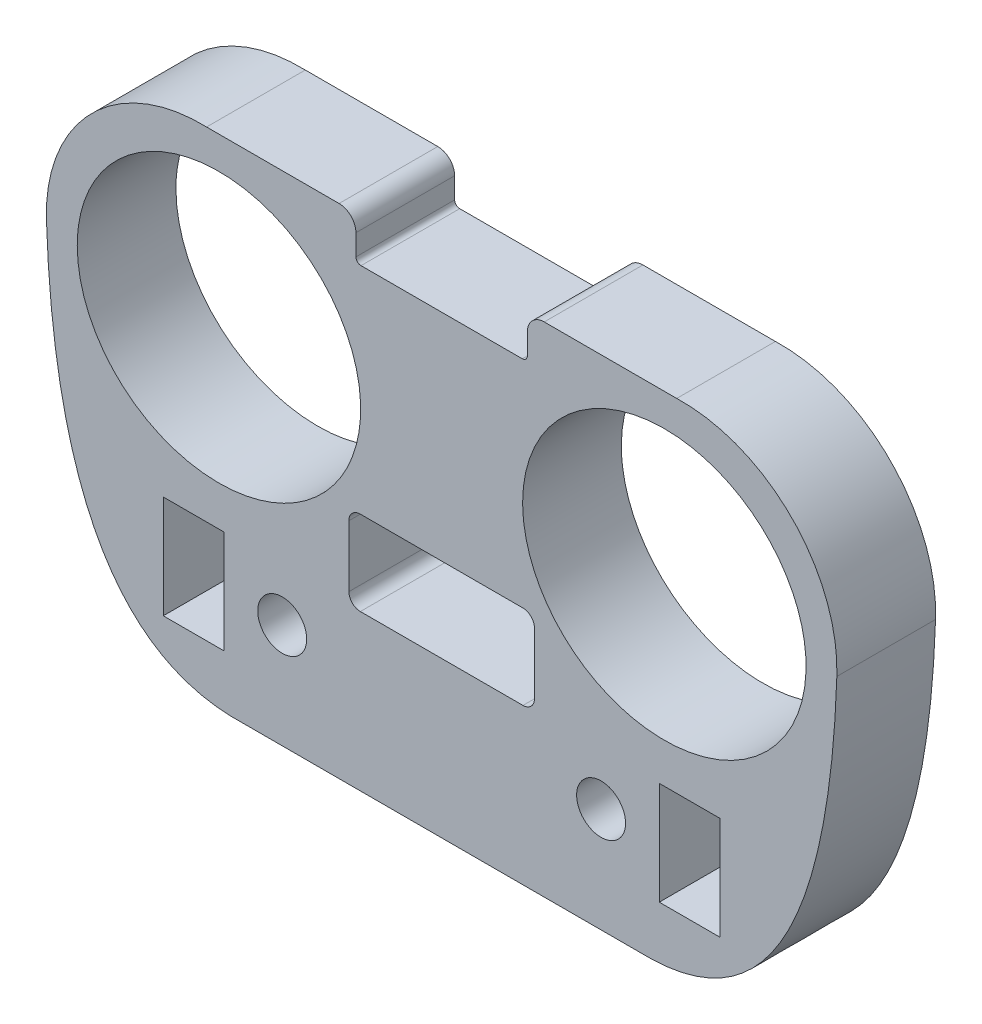
SolidWorks part; units mm, degrees
material "Acrylic (Medium-high impact)"
ref_plane "Front Plane" through (0, 0, 0) normal (0, 0, 1) x (1, 0, 0)
ref_plane "Top Plane" through (0, 0, 0) normal (0, 1, 0) x (1, 0, 0)
ref_plane "Right Plane" through (0, 0, 0) normal (1, 0, 0) x (0, 0, -1)
sketch "Model" plane through (0, 0, 0) normal (0, 0, 1) x (1, 0, 0)
  line L0 (549.8561, 574.3347) -> (554.6761, 574.3347)
  line L1 (554.6761, 576.8347) -> (549.1761, 576.8347) construction
  line L2 (554.6761, 576.8347) -> (560.1761, 576.8347) construction
  line L3 (554.6761, -405.4445) -> (554.6761, 49594.5555) construction
  line L4 (540.7427, 594.6497) -> (549.5961, 594.6497)
  line L5 (542.1922, 565.1247) -> (567.16, 565.1247)
  line L6 (549.8561, 579.3347) -> (554.6761, 579.3347)
  line L7 (567.5761, 574.3747) -> (567.5761, 568.2747)
  line L8 (571.1761, 574.3747) -> (567.5761, 574.3747)
  line L9 (571.1761, 568.2747) -> (571.1761, 574.3747)
  line L10 (567.5761, 568.2747) -> (571.1761, 568.2747)
  line L11 (560.1761, 578.6547) -> (560.1761, 575.0147)
  line L12 (559.4961, 579.3347) -> (554.6761, 579.3347)
  line L13 (559.4961, 574.3347) -> (554.6761, 574.3347)
  line L14 (538.7761, 571.3247) -> (570.5761, 571.3247) construction
  line L15 (541.4761, 584.7347) -> (567.8761, 584.7347) construction
  line L16 (549.5961, 592.1097) -> (559.7561, 592.1097)
  line L17 (549.5961, 592.1097) -> (549.5961, 594.6497)
  line L18 (559.7561, 592.1097) -> (559.7561, 594.6497)
  line L19 (559.7561, 594.6497) -> (568.6095, 594.6497)
  line L20 (541.4761, 584.7347) -> (541.4761, 592.7347) construction
  line L21 (549.1761, 578.6547) -> (549.1761, 575.0147)
  line L32 (541.7761, 568.2747) -> (538.1761, 568.2747)
  line L33 (538.1761, 568.2747) -> (538.1761, 574.3747)
  line L34 (538.1761, 574.3747) -> (541.7761, 574.3747)
  line L35 (541.7761, 574.3747) -> (541.7761, 568.2747)
  circle A0 centre (545.2261, 571.3247) radius 1.45
  arc A1 (578.1008, 585.1247) -> (568.6095, 594.6497) centre (568.8929, 585.4407) ccw
  arc A3 (549.1761, 575.0147) -> (549.8561, 574.3347) centre (549.8561, 575.0147) ccw
  arc A4 (549.1761, 578.6547) -> (549.8561, 579.3347) centre (549.8561, 578.6547) cw
  arc A5 (560.1761, 578.6547) -> (559.4961, 579.3347) centre (559.4961, 578.6547) ccw
  arc A6 (560.1761, 575.0147) -> (559.4961, 574.3347) centre (559.4961, 575.0147) cw
  arc A7 (531.2514, 585.1247) -> (540.7427, 594.6497) centre (540.4593, 585.4407) cw
  circle A9 centre (564.1261, 571.3247) radius 1.45
  ellipse E0 centre (541.4761, 584.7347) end of major axis (533.0761, 584.7347) minor radius 8
  ellipse E1 centre (567.8761, 584.7347) end of major axis (559.4761, 584.7347) minor radius 8
  spline S0 degree 2 poles (578.1008, 585.1247) (577.4253, 565.4445) (567.16, 565.1247) knots 0 0 0 1 1 1
  spline S48 degree 2 poles (531.2514, 585.1247) (531.9269, 565.4445) (542.1922, 565.1247) knots 0 0 0 1 1 1
  point P0 (554.6761, 571.3247)
  point P2 (541.4761, 592.7347)
  point P19 (549.8761, 584.7347)
  point P32 (559.4761, 584.7347)
  point P33 (554.6761, 584.7347)
  point P34 (554.6761, 565.1247)
  point P36 (554.6761, 576.8347)
  point P40 (554.6761, 592.1097)
  dimension "D11" = 2.9
  dimension "D12" = 8
  dimension "D14" = 0.68
  dimension "D16" = 10.16
  dimension "D1" = 3.45
  dimension "D2" = 9.45
  dimension "D3" = 20
  dimension "D4" = 6.1
  dimension "D5" = 11
  dimension "D6" = 5
  dimension "D7" = 3.6
  dimension "D8" = 29.525
  dimension "D9" = 6.2
  dimension "D10" = 0.04
  dimension "D13" = 13.2
  dimension "D15" = 7.9
  dimension "D17" = 2.54
  dimension "D18" = 5.51
  dimension "D19" = 8.4
extrude "Boss-Extrude1" add sketch "Model" along normal blind 5.85 contours A7 S48 L5 S0 A1 L4 A9 L11 A6 L13 L0 A3 L21 A4 L6 L12 A5 E0 A0 L10 L7 L8 L9 L34 L35 L32 L33 E1 region at (545.1694, 594.0958, 0)
fillet "Fillet1" radius 0.3 2 edges at (559.7561, 592.1097, 2.925) (549.5961, 592.1097, 2.925)
fillet "Fillet2" radius 1 2 edges at (559.7561, 594.6497, 2.925) (549.5961, 594.6497, 2.925)
